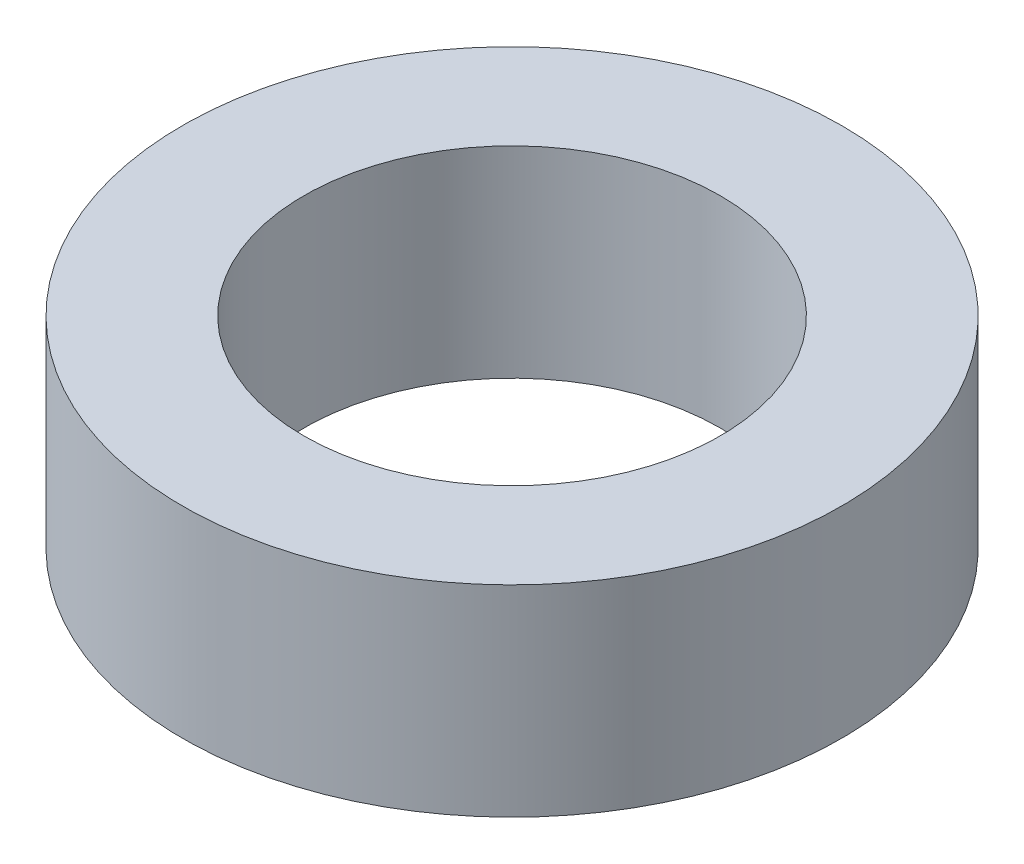
SolidWorks part; units mm, degrees
ref_plane "Front Plane" through (0, 0, 0) normal (0, 0, 1) x (1, 0, 0)
ref_plane "Top Plane" through (0, 0, 0) normal (0, 1, 0) x (1, 0, 0)
ref_plane "Right Plane" through (0, 0, 0) normal (1, 0, 0) x (0, 0, -1)
sketch "Sketch1" plane through (0, 0, 0) normal (0, 1, 0) x (1, 0, 0)
  circle A0 centre (0, 0) radius 47.5
  dimension "FLANGE_OD" = 95
extrude "Boss-Extrude1" add sketch "Sketch1" along normal blind 29
sketch "Sketch2" plane through (0, 0, 0) normal (0, 1, 0) x (1, 0, 0)
  circle A0 centre (0, 0) radius 30
  dimension "BORE_D" = 60
extrude "Cut-Extrude1" cut sketch "Sketch2" along normal through all
sketch "Sketch3" plane through (0, 29, 0) normal (0, 1, 0) x (1, 0, 0)
  circle A0 centre (0, 0) radius 21.476 construction
  circle A1 centre (-21.476, 0) radius 1.7462
  dimension "BOLT_D" = 3.4923
  dimension "BOLT_PCD" = 42.952
extrude "Cut-Extrude2" cut sketch "Sketch3" against normal blind 26.7385 rebuild error yes
pattern_circular "CirPattern1" count 8 over 360 rebuild error yes
